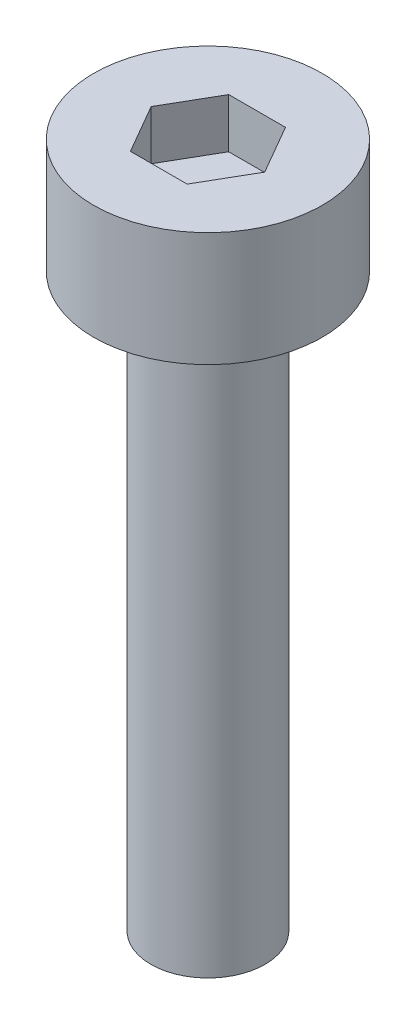
SolidWorks part; units mm, degrees
ref_plane "Front Plane" through (0, 0, 0) normal (0, 0, 1) x (1, 0, 0)
ref_plane "Top Plane" through (0, 0, 0) normal (0, 1, 0) x (1, 0, 0)
ref_plane "Right Plane" through (0, 0, 0) normal (1, 0, 0) x (0, 0, -1)
sketch "Sketch1" plane through (0, 0, 0) normal (0, 1, 0) x (1, 0, 0)
  circle A0 centre (0, 0) radius 1.5
  dimension "D1" = 3
extrude "ScrewShaft" add sketch "Sketch1" along normal blind 15
sketch "Sketch2" plane through (0, 15, 0) normal (0, 1, 0) x (1, 0, 0)
  circle A0 centre (0, 0) radius 3
  dimension "D1" = 6
extrude "Boss-Extrude2" add sketch "Sketch2" along normal blind 3
sketch "Sketch3" plane through (0, 18, 0) normal (0, 1, 0) x (1, 0, 0)
  line L0 (0, 0) -> (0, 1.29) construction
  line L1 (1.4896, 0) -> (0.7448, 1.29)
  line L2 (0.7448, 1.29) -> (-0.7448, 1.29)
  line L3 (-0.7448, 1.29) -> (-1.4896, 0)
  line L4 (-1.4896, 0) -> (-0.7448, -1.29)
  line L5 (-0.7448, -1.29) -> (0.7448, -1.29)
  line L6 (0.7448, -1.29) -> (1.4896, 0)
  circle A0 centre (0, 0) radius 1.29 construction
  dimension "D1" = 2.58
extrude "Cut-Extrude1" cut sketch "Sketch3" against normal blind 1.3
equation "\"X-ROD-SPACING\"=45"
equation "\"Y-ROD-SPACING\"=75"
equation "\"Z-ROD-SPACING\"=17.5"
equation "\"Y-BED-OFFSET\"=2"
equation "\"Y-BED-ROD-INSET\"=3.5"
equation "\"T-SLOT-NUT-FILLET-RADIUS\"=0.5"
equation "\"T-SLOT-SCREW-SHAFT-RADIUS\"=1.55"
equation "\"T-SLOT-SCREW-SHAFT-CUTOUT-LENGTH\"=11"
equation "\"T-SLOT-NUT-DEPTH\"=3.5"
equation "\"T-SLOT-NUT-WIDTH\"=2.85"
equation "\"T-SLOT-NUT-END-DISTANCE\"=8"
equation "\"ACRYLIC-THICKNESS\"=10"
equation "\"ACRYLIC-THICKNESS2\"=4.5"
equation "\"ACRYLIC-TAB-CUTOUT-SIZE\"=\"ACRYLIC-THICKNESS\"+\"ACRYLIC-TAB-TOLERANCE\"*2"
equation "\"ACRYLIC-TAB-WIDTH\"=\"ACRYLIC-THICKNESS\""
equation "\"ACRYLIC-M3-HOLE\"=2.9"
equation "\"SMOOTHROD-CAP-SCREW-DISTANCE\"=20"
equation "\"FRAME-WIDTH-INNER\"=370"
equation "\"NEMA17-HOLE-SPACING\"=31"
equation "\"NEMA17-CENTRAL-CUTOUT\"=22.5"
equation "\"Z-BRACKET-REACH\"=55"
equation "\"TOP-BRACKET-SPACING\"=40"
equation "\"SMOOTHROD-X-LENGTH\"=350"
equation "\"SMOOTHROD-Y-LENGTH\"=350"
equation "\"SMOOTHROD-Z-LENGTH\"=350"
equation "\"SMOOTHROD-TIGHTENING-HEADROOM\"=.25"
equation "\"LEADSCREW-Z-LENGTH\"=300"
equation "\"SCREW-LENGTH-FRAME\"=\"ACRYLIC-THICKNESS\" + 10"
equation "\"SCREW-HEAD-RADIUS\"=6"
equation "\"PRINTED-X-SMOOTHROD-DIAMETER\"=8.8"
equation "\"PRINTED-X-SMOOTHROD-CUTOUT\"=10"
equation "\"PRINTED-X-BASE-HEIGHT\"=10"
equation "\"PRINTED-LM8UU-CUTOUT-SIZE\"=15.5"
equation "\"PRINTED-LM8UU-CUTOUT-LENGTH\"=24.5"
equation "\"PRINTED-X-IDLER-HEIGHT\"=16"
equation "\"PSU-MOUNTING-WIDTH\"=95"
equation "\"PSU-MOUNTING-HEIGHT\"=177"
equation "\"D1@ScrewShaft\"=\"SCREW-LENGTH-MOTOR\""
equation "\"D1@Sketch2\"=\"SCREW-HEAD-RADIUS\""
equation "\"Y-BED-SCREW-SPACING\"=209"
equation "\"Y-BED-SCREW-CUTOUT-SLOT-HEIGHT\"=2"
equation "\"Z-ROD-INSET\"=13.5"
equation "\"SCREW-LENGTH-MOTOR\"=\"ACRYLIC-THICKNESS\" + 5"
equation "\"Y-BELT-TO-ROD-DISTANCE\"=20"
equation "\"SPOOL-HOLDER-ROD-SPACING\"=150"
